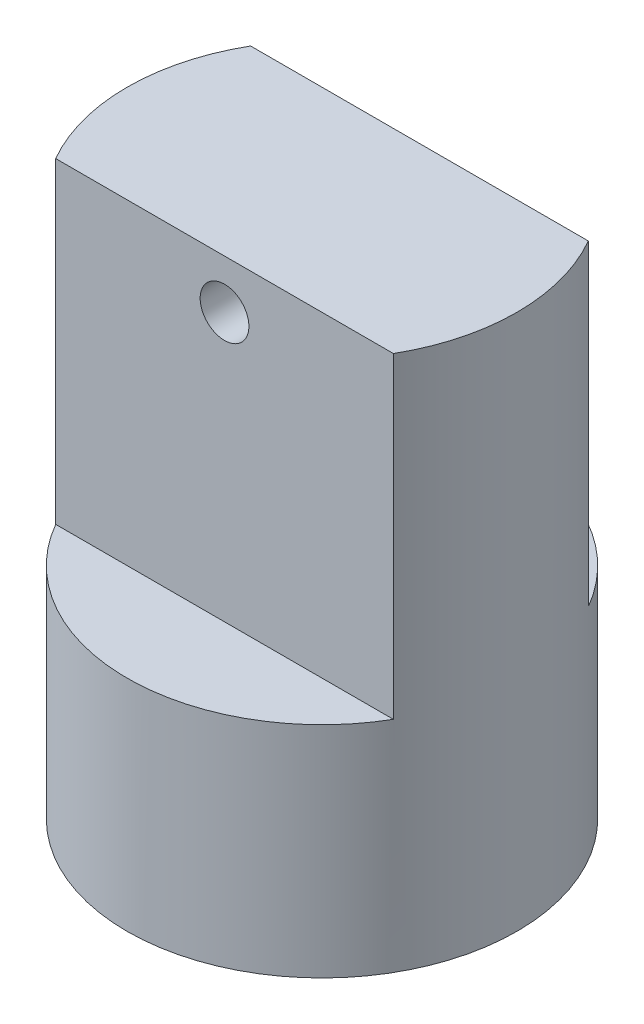
SolidWorks part; units mm, degrees
ref_plane "Front Plane" through (0, 0, 0) normal (0, 0, 1) x (1, 0, 0)
ref_plane "Top Plane" through (0, 0, 0) normal (0, 1, 0) x (1, 0, 0)
ref_plane "Right Plane" through (0, 0, 0) normal (1, 0, 0) x (0, 0, -1)
sketch "Sketch1" plane through (0, 0, 0) normal (0, 1, 0) x (1, 0, 0)
  circle A0 centre (0, 0) radius 50.8
  dimension "D1" = 101.6
extrude "Boss-Extrude1" add sketch "Sketch1" along normal blind 139.7
sketch "Sketch2" plane through (0, 0, 0) normal (0, 0, 1) x (1, 0, 0)
  line L0 (50.8, 139.7) -> (-50.8, 139.7) construction
  line L1 (-50.8, 222.25) -> (50.8, 222.25)
  line L2 (-50.8, 222.25) -> (-50.8, 57.15)
  line L3 (-50.8, 57.15) -> (50.8, 57.15)
  line L4 (50.8, 222.25) -> (50.8, 57.15)
  line L5 (-50.8, 222.25) -> (50.8, 57.15) construction
  line L6 (-50.8, 57.15) -> (50.8, 222.25) construction
  line L7 (50.8, 0) -> (50.8, 139.7) construction
  point P0 (0, 139.7)
  dimension "D1" = 165.1
extrude "Cut-Extrude1" cut sketch "Sketch2" along normal blind 50.8 from offset 25.4
extrude "Cut-Extrude2" cut sketch "Sketch2<2>" against normal blind 50.8 from offset 25.4 offset against normal yes
sketch "Sketch2<2>" plane through (0, 0, 0) normal (0, 0, 1) x (1, 0, 0) same geometry as "Sketch2"
sketch "Sketch3" plane through (0, 0, 0) normal (0, -1, 0) x (1, 0, 0)
  circle A0 centre (0, 0) radius 6.35
  dimension "D1" = 12.7
extrude "Cut-Extrude3" cut sketch "Sketch3" against normal blind 25.4
sketch "Sketch4" plane through (0, 0, 25.4) normal (0, 0, 1) x (1, 0, 0)
  line L0 (-43.9941, 139.7) -> (43.9941, 139.7) construction
  circle A0 centre (0, 127) radius 6.35
  dimension "D2" = 12.7
  dimension "D1" = 12.7
extrude "Cut-Extrude4" cut sketch "Sketch4" against normal through all
